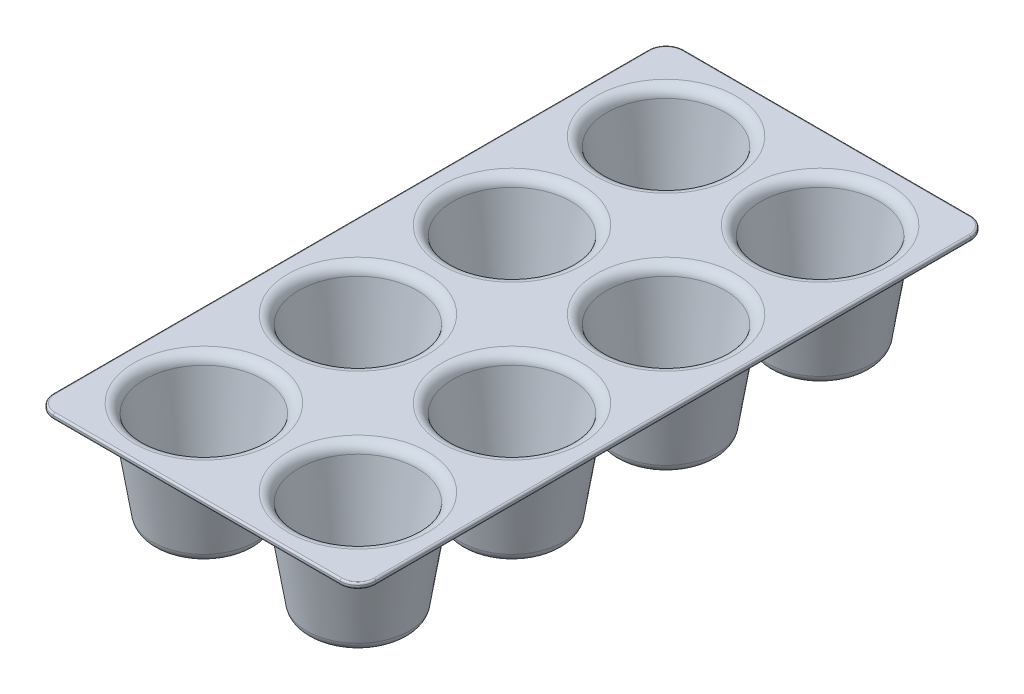
SolidWorks part; units mm, degrees
ref_plane "Front Plane" through (0, 0, 0) normal (0, 0, 1) x (1, 0, 0)
ref_plane "Top Plane" through (0, 0, 0) normal (0, 1, 0) x (1, 0, 0)
ref_plane "Right Plane" through (0, 0, 0) normal (1, 0, 0) x (0, 0, -1)
sketch "Sketch1" plane through (0, 0, 0) normal (0, 0, 1) x (1, 0, 0)
  line L1 (36.0369, -2.5307) -> (28.5283, -49.9386)
  line L2 (22.6021, -55) -> (-22.6021, -55)
  line L3 (-28.5283, -49.9386) -> (-36.0369, -2.5307)
  line L4 (0, 0) -> (0, -72.3175) construction
  line L5 (-39, 0) -> (-39.4465, 0)
  line L6 (39, 0) -> (39.4465, 0)
  line L7 (39, 3) -> (39.4465, 3)
  line L8 (33.0739, -2.0614) -> (25.5652, -49.4693)
  line L9 (22.6021, -52) -> (-22.6021, -52)
  line L10 (-25.5652, -49.4693) -> (-33.0739, -2.0614)
  line L11 (-39, 3) -> (-39.4465, 3)
  line L12 (39.4465, 0) -> (39.4465, 3)
  line L13 (-39.4465, 0) -> (-39.4465, 3)
  line L14 (-39, 3) -> (-39, 0)
  line L15 (0, -55) -> (0, -52)
  line L16 (0, -52) -> (0, 3)
  line L17 (0, 3) -> (-39, 3)
  arc A0 (-39, 0) -> (-36.0369, -2.5307) centre (-39, -3) cw
  arc A1 (39, 0) -> (36.0369, -2.5307) centre (39, -3) ccw
  arc A2 (-22.6021, -55) -> (-28.5283, -49.9386) centre (-22.6021, -49) cw
  arc A3 (28.5283, -49.9386) -> (22.6021, -55) centre (22.6021, -49) cw
  arc A4 (39, 3) -> (33.0739, -2.0614) centre (39, -3) ccw
  arc A5 (25.5652, -49.4693) -> (22.6021, -52) centre (22.6021, -49) cw
  arc A6 (-22.6021, -52) -> (-25.5652, -49.4693) centre (-22.6021, -49) cw
  arc A7 (-39, 3) -> (-33.0739, -2.0614) centre (-39, -3) cw
  point P4 (0, 0)
  dimension "D2" = 3
  dimension "D3" = 6
  dimension "D1" = 18
  dimension "D5" = 58
  dimension "D6" = 78
  dimension "D4" = 3
revolve "Revolve1" add sketch "Sketch1" angle 360 about L15 region at (-11.3011, -54.3011, 0)
ref_plane "Plane1" through (0, 3, 0) normal (0, -1, 0) x (-1, 0, 0)
sketch "Sketch2" plane through (0, 3, 0) normal (0, -1, 0) x (-1, 0, 0)
  line L0 (43, 47) -> (43, -305) construction
  line L1 (-37, 47) -> (123, 47)
  line L2 (-47, 37) -> (-47, -295)
  line L3 (-37, -305) -> (123, -305)
  line L4 (133, 37) -> (133, -295)
  line L5 (0, 0) -> (0, -103.8013) construction
  line L7 (86, 0) -> (86, -103.8013) construction
  arc A1 (123, -305) -> (133, -295) centre (123, -295) ccw
  arc A2 (-47, -295) -> (-37, -305) centre (-37, -295) ccw
  arc A3 (-37, 47) -> (-47, 37) centre (-37, 37) ccw
  arc A4 (123, 47) -> (133, 37) centre (123, 37) cw
  point P9 (0, 0)
  point P11 (0, 0)
  point P12 (0, 0)
  point P15 (0, 0)
  dimension "D5" = 10
  dimension "D1" = 86
  dimension "D2" = 47
  dimension "D3" = 47
  dimension "D4" = 305
extrude "Boss-Extrude1" add sketch "Sketch2" along normal blind 3
fillet "Fillet1" radius 1 16 edges at (44.0711, 0, -44.0711) (-43, 0, -47) (-130.0711, 0, -44.0711) (-133, 0, 129) (-130.0711, 0, 302.0711) (-43, 0, 305) (44.0711, 0, 302.0711) (44.0711, 3, -44.0711) (-43, 3, -47) (-130.0711, 3, -44.0711) (-133, 3, 129) (-130.0711, 3, 302.0711) (-43, 3, 305) (44.0711, 3, 302.0711) (47, 0, 129) (47, 3, 129)
revolve "Cut-Revolve2" cut sketch "Sketch1<5>" angle 360 about L4 region at (-14.9241, -23.0429, 0)
sketch "Sketch1<5>" plane through (0, 0, 0) normal (0, 0, 1) x (1, 0, 0) same geometry as "Sketch1"
pattern_linear "LPattern1" count 2 spacing 86 along (-1, 0, 0) count 4 spacing 86 along (0, 0, 1) of "Revolve1", "Cut-Revolve2"
